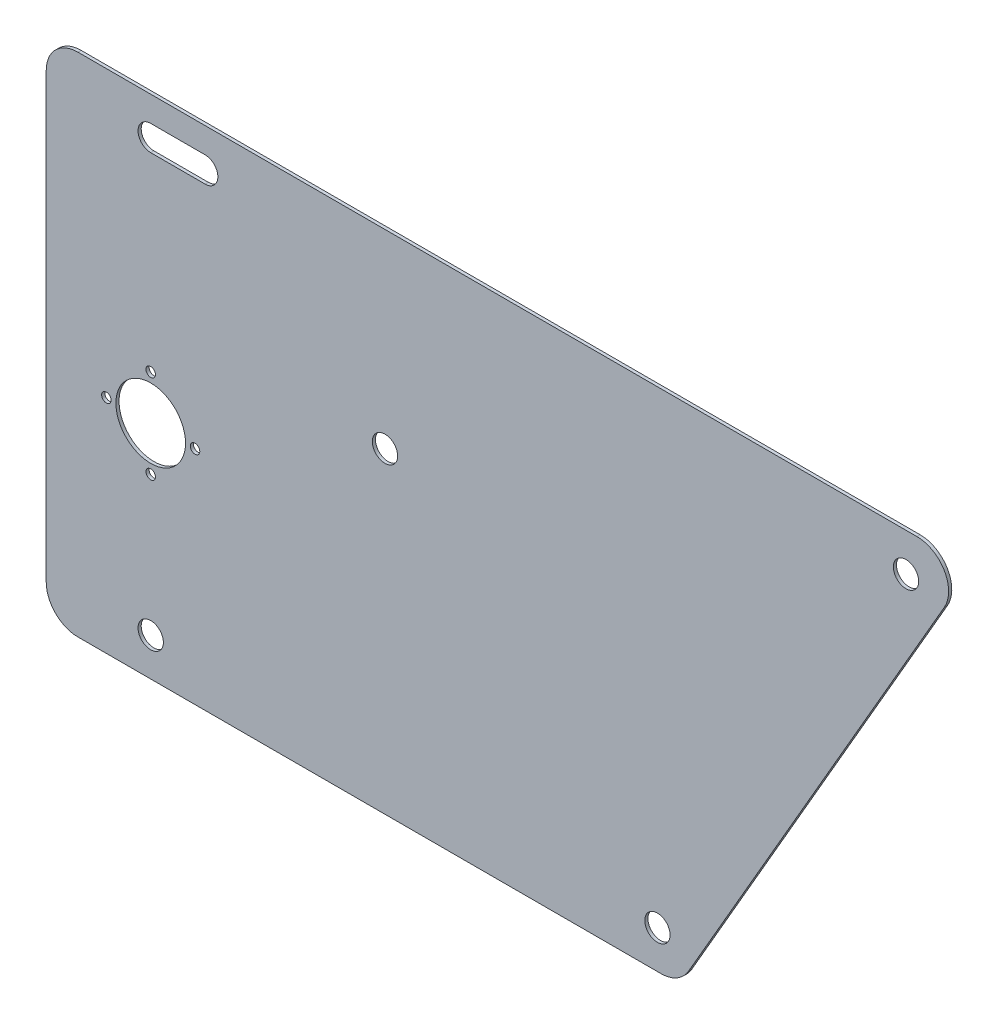
SolidWorks part; units mm, degrees
ref_plane "Front Plane" through (0, 0, 0) normal (0, 0, 1) x (1, 0, 0)
ref_plane "Top Plane" through (0, 0, 0) normal (0, 1, 0) x (1, 0, 0)
ref_plane "Right Plane" through (0, 0, 0) normal (1, 0, 0) x (0, 0, -1)
sketch "Sketch1" plane through (0, 0, 0) normal (0, 0, 1) x (1, 0, 0)
  line L0 (100, 80) -> (192.376, 80)
  line L1 (-100, -80) -> (100, -80)
  line L2 (-100, -80) -> (-100, 80)
  line L3 (-100, 80) -> (100, 80)
  line L4 (100, -80) -> (100, 80)
  line L5 (-100, -80) -> (100, 80) construction
  line L6 (-100, 80) -> (100, -80) construction
  line L7 (192.376, 80) -> (100, -80)
  line L8 (100, 80) -> (100, -80)
  point P0 (0, 0)
  dimension "D1" = 160
  dimension "D2" = 200
  dimension "D3" = 30
extrude "Boss-Extrude1" add sketch "Sketch1" along normal blind 1 contours L1 L4 L3 L2 | L7 L0 L4 region at (0, 0, 0) region at (130.792, 26.6667, 0)
fillet "Fillet1" radius 10 4 edges at (192.376, 80, 0.5) (100, -80, 0.5) (-100, -80, 0.5) (-100, 80, 0.5)
sketch "Sketch2" plane through (0, 0, 1) normal (0, 0, 1) x (1, 0, 0)
  line L0 (-90, -80) -> (94.2265, -80) construction
  line L1 (183.7158, 65) -> (102.8868, -75) construction
  line L2 (-90, 80) -> (175.0555, 80) construction
  line L4 (-67, 68) -> (-49.7837, 68) construction
  line L7 (-100, -70) -> (-100, 70) construction
  line L9 (-67, 72) -> (-49.7837, 72)
  line L10 (-67, 64) -> (-49.7837, 64)
  circle A0 centre (93.0718, -68) radius 4
  circle A1 centre (171.5914, 68) radius 4
  circle A2 centre (-67, -10) radius 11
  circle A3 centre (-67, -68) radius 4
  circle A4 centre (-53, -10) radius 1.5
  circle A5 centre (-67, 4) radius 1.5
  circle A6 centre (-81, -10) radius 1.5
  circle A7 centre (-67, -24) radius 1.5
  circle A10 centre (6.9988, 20) radius 4
  arc A11 (-67, 72) -> (-67, 64) centre (-67, 68) ccw
  arc A12 (-49.7837, 64) -> (-49.7837, 72) centre (-49.7837, 68) ccw
  point P12 (-58.3919, 68)
  dimension "D3" = 8
  dimension "D4" = 8
  dimension "D9" = 22
  dimension "D10" = 8
  dimension "D12" = 3
  dimension "D13" = 3
  dimension "D14" = 3
  dimension "D15" = 3
  dimension "D16" = 14
  dimension "D20" = 4
  dimension "D22" = 8
  dimension "D1" = 12
  dimension "D2" = 12
  dimension "D5" = 12
  dimension "D6" = 12
  dimension "D7" = 33
  dimension "D8" = 70
  dimension "D11" = 12
  dimension "D17" = 14
  dimension "D18" = 14
  dimension "D19" = 14
  dimension "D24" = 60
extrude "Cut-Extrude1" cut sketch "Sketch2" against normal blind 3
